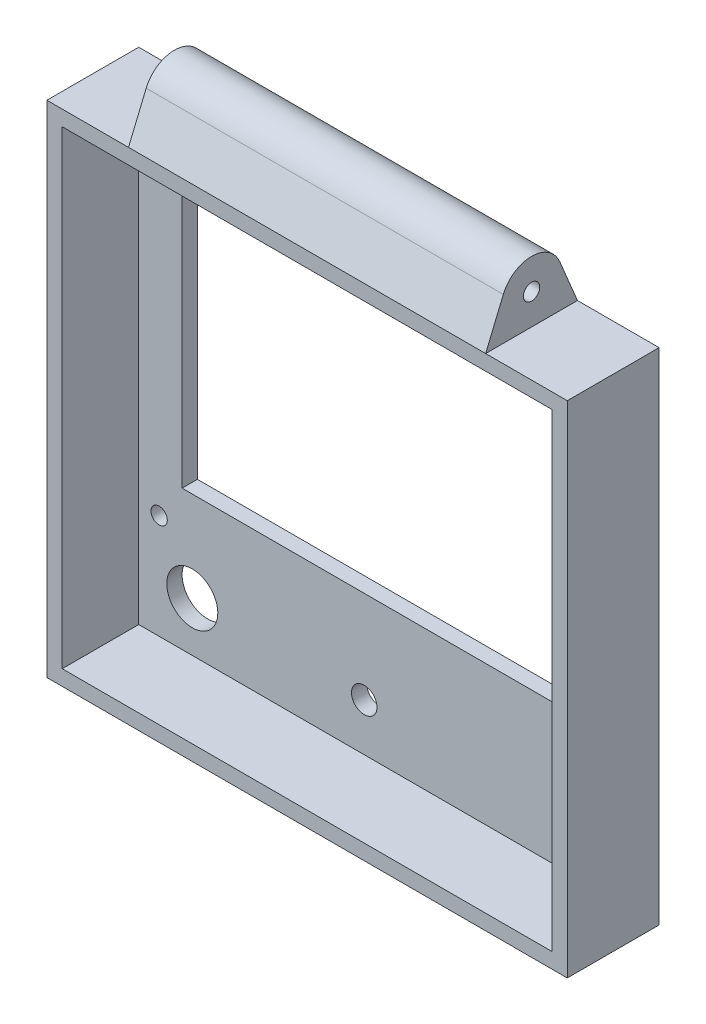
SolidWorks part; units mm, degrees
ref_plane "Plano frontal" through (0, 0, 0) normal (0, 0, 1) x (1, 0, 0)
ref_plane "Plano superior" through (0, 0, 0) normal (0, 1, 0) x (1, 0, 0)
ref_plane "Plano direito" through (0, 0, 0) normal (1, 0, 0) x (0, 0, -1)
sketch "Esboço2" plane through (0, 0, 0) normal (1, 0, 0) x (0, 0, -1)
  line L0 (0, 0) -> (18, 0)
  line L2 (18, 0) -> (18, 98)
  line L3 (18, 98) -> (0, 98)
  line L4 (0, 98) -> (0, 0)
  point P3 (70.0916, 9.7402)
  point P7 (39.3892, 0)
  point P8 (51.3708, -2.9278)
  point P9 (41.584, 0)
  dimension "D1" = 98
  dimension "D3" = 18
extrude "Ressalto-extrusão1" add sketch "Esboço2" along normal mid plane 102
shell "Casca1" thickness 3 removed face at (0, 49, 0)
sketch "Esboço4" plane through (0, 0, -18) normal (0, 0, -1) x (1, 0, 0)
  line L0 (51, -98) -> (-51, -98) construction
  line L1 (39.5, -82) -> (-39.5, -82)
  line L2 (39.5, -82) -> (39.5, -30.4)
  line L3 (39.5, -30.4) -> (-39.5, -30.4)
  line L4 (-39.5, -82) -> (-39.5, -30.4)
  line L5 (39.5, -82) -> (-39.5, -30.4) construction
  line L6 (39.5, -30.4) -> (-39.5, -82) construction
  line L8 (44, -23.5) -> (-44, -23.5) construction
  line L9 (44, -23.5) -> (44, -88.5) construction
  line L10 (44, -88.5) -> (-44, -88.5) construction
  line L11 (-44, -23.5) -> (-44, -88.5) construction
  line L12 (44, -23.5) -> (-44, -88.5) construction
  line L13 (44, -88.5) -> (-44, -23.5) construction
  circle A0 centre (-44, -23.5) radius 1.6
  circle A1 centre (-44, -88.5) radius 1.6
  circle A2 centre (44, -88.5) radius 1.6
  circle A3 centre (44, -23.5) radius 1.6
  circle A4 centre (-37.5, -12.7) radius 5
  circle A5 centre (36.75, -15.3) radius 3
  circle A6 centre (-3.8, -12.3) radius 2.5
  point P0 (0, -56.2)
  point P9 (0, -56)
  dimension "D7" = 3.2
  dimension "D11" = 10
  dimension "D14" = 6
  dimension "D16" = 5
  dimension "D1" = 51.6
  dimension "D2" = 79
  dimension "D3" = 16
  dimension "D4" = 65
  dimension "D5" = 88
  dimension "D6" = 6.5
  dimension "D8" = 75.8
  dimension "D9" = 6.5
  dimension "D10" = 7.25
  dimension "D12" = 76.2
  dimension "D13" = 40.2
  dimension "D15" = 8.2
extrude "Corte-extrusão1" cut sketch "Esboço4" against normal up to surface (3 mm away) up to face at (0, 49, -15)
sketch "Esboço5" plane through (51, 0, 0) normal (1, 0, 0) x (0, 0, -1)
  line L0 (14.5385, 106.3077) -> (18, 98)
  line L1 (18, 98) -> (0, 98)
  line L2 (0, 98) -> (3.4615, 106.3077)
  arc A0 (14.5385, 106.3077) -> (3.4615, 106.3077) centre (9, 104) ccw
  circle A1 centre (9, 104) radius 1.6
  point P9 (9, 98)
  dimension "D1" = 12
  dimension "D2" = 3.2
extrude "Ressalto-extrusão2" add sketch "Esboço5" against normal through all
sketch "Esboço6" plane through (0, 0, -18) normal (0, 0, -1) x (-1, 0, 0)
  line L0 (-51, 98) -> (51, 98) construction
  line L1 (-35, 110) -> (35, 110) construction
  line L2 (-35, 98) -> (-35, 110)
  line L3 (35, 98) -> (51, 98)
  line L4 (35, 98) -> (35, 110)
  line L5 (35, 110) -> (51, 110)
  line L6 (-51, 98) -> (-35, 98)
  line L7 (-51, 98) -> (-51, 110)
  line L8 (-51, 110) -> (-35, 110)
  line L9 (51, 98) -> (51, 110)
  line L10 (51, 110) -> (-51, 110) construction
  line L11 (51, 0) -> (51, 98) construction
  point P6 (0, 110)
  point P8 (0, 98)
  point P15 (47.2024, 110)
  point P16 (51, 98)
  point P17 (51, 98)
  dimension "D1" = 70
extrude "Corte-extrusão2" cut sketch "Esboço6" against normal through all
